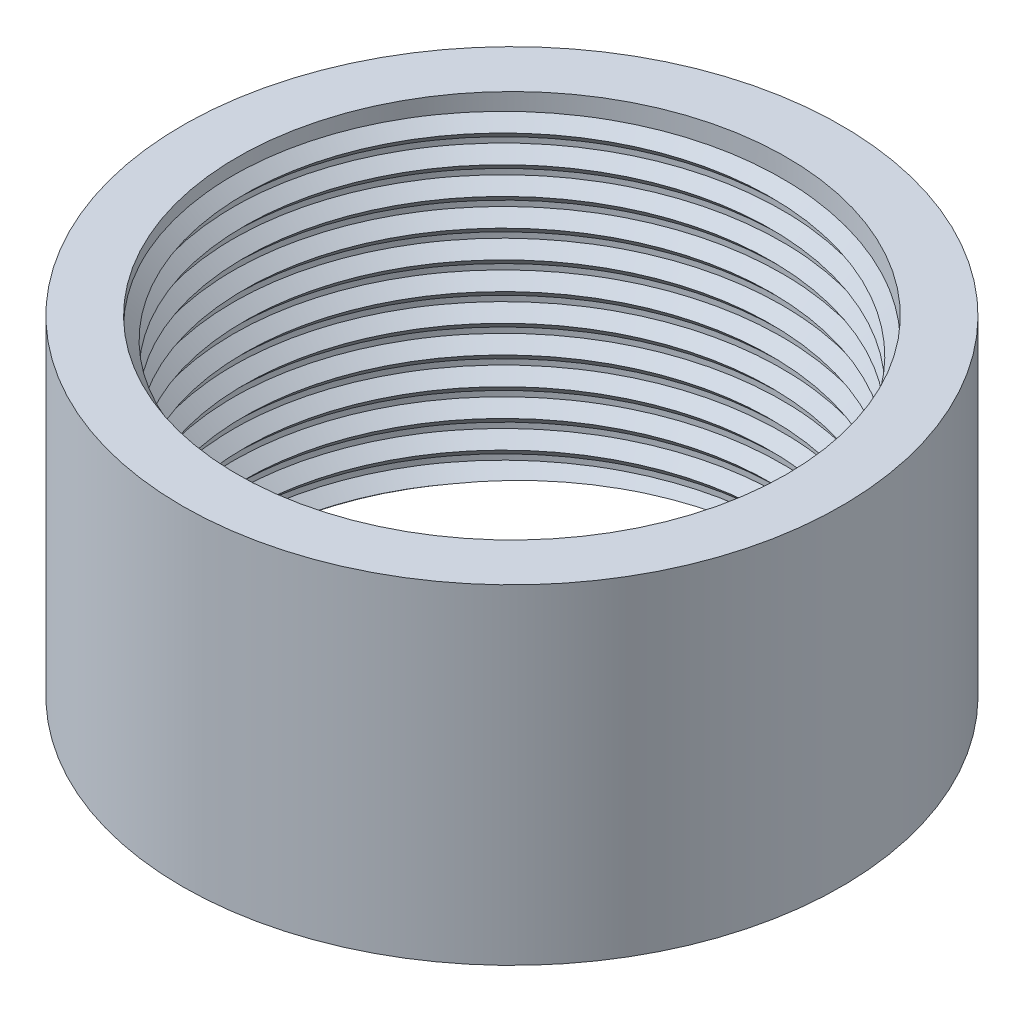
SolidWorks part; units mm, degrees
ref_plane "Front Plane" through (0, 0, 0) normal (0, 0, 1) x (1, 0, 0)
ref_plane "Top Plane" through (0, 0, 0) normal (0, 1, 0) x (1, 0, 0)
ref_plane "Right Plane" through (0, 0, 0) normal (1, 0, 0) x (0, 0, -1)
sketch "Sketch1" plane through (0, 0, 0) normal (0, 1, 0) x (1, 0, 0)
  circle A0 centre (0, 0) radius 3
  circle A1 centre (0, 0) radius 2.5
  dimension "D1" = 6
  dimension "D2" = 5
extrude "Boss-Extrude1" add sketch "Sketch1" along normal blind 3
sketch "Sketch2" plane through (0, 0, 0) normal (0, 0, 1) x (1, 0, 0)
  line L0 (0, 3) -> (3, 3) construction
  line L1 (3, 3) -> (-3, 3) construction
  line L2 (3, 3) -> (3, 0) construction
  line L3 (3, 0) -> (2.5, 0) construction
  line L4 (-3, 0) -> (3, 0) construction
  line L5 (2.5, 0) -> (2.5, 3) construction
  line L6 (2.5, 3) -> (2.4, 2.9)
  line L7 (2.4, 2.9) -> (2.5, 2.8)
  line L8 (2.5, 2.8) -> (2.5, 3)
  line L9 (2.4, 2.9) -> (2.5, 2.9) construction
  dimension "D1" = 0.5
  dimension "D2" = 45
  dimension "D3" = 45
  dimension "D4" = 0.1
sketch "Sketch3" plane through (0, 3, 0) normal (0, 1, 0) x (1, 0, 0)
  circle A0 centre (0, 0) radius 2.5 construction
  circle A1 centre (0, 0) radius 2.5
curve "Helix/Spiral1" pitch 0.25 height 3.75 radius 2.5 centre (0, 3, 0) axis (0, -1, 0) start towards (1, 0, 0)
sweep "Sweep1" add profiles "Sketch2" path "Helix/Spiral1"
sketch "Sketch4" plane through (0, 0, 0) normal (0, -1, 0) x (1, 0, 0)
  circle A0 centre (0, 0) radius 3.6041
extrude "Cut-Extrude1" cut sketch "Sketch4" along normal blind 4
